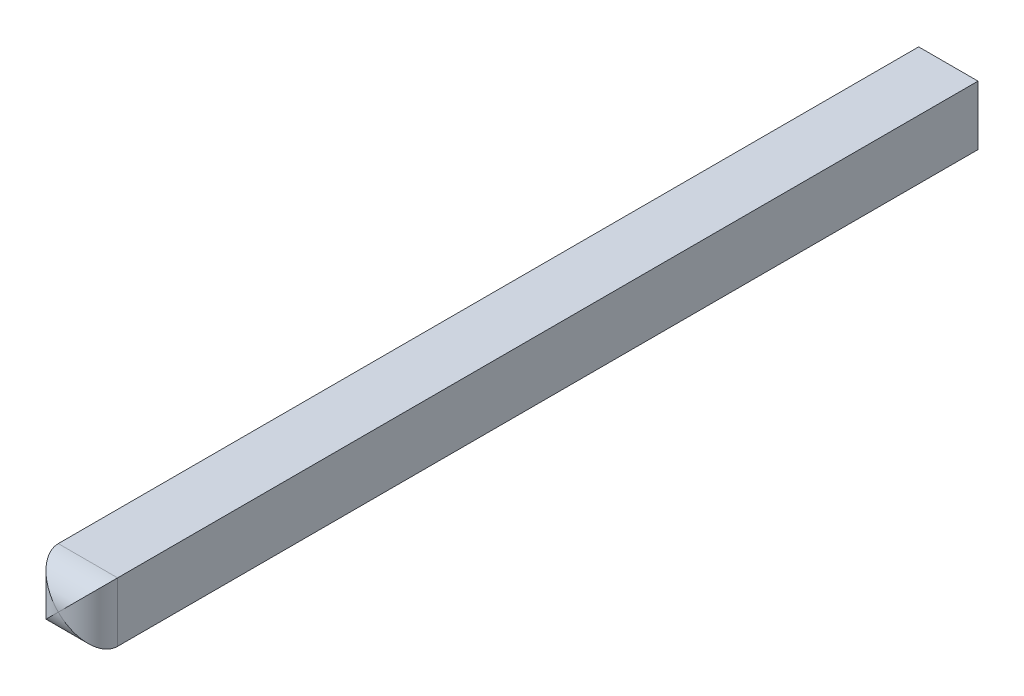
SolidWorks part; units mm, degrees
ref_plane "Front Plane" through (0, 0, 0) normal (0, 0, 1) x (1, 0, 0)
ref_plane "Top Plane" through (0, 0, 0) normal (0, 1, 0) x (1, 0, 0)
ref_plane "Right Plane" through (0, 0, 0) normal (1, 0, 0) x (0, 0, -1)
sketch "Sketch1" plane through (0, 0, 0) normal (0, 0, 1) x (1, 0, 0)
  line L0 (-11.7143, 10.1429) -> (-11.7143, -9.8571)
  line L1 (-11.7143, -9.8571) -> (8.2857, -9.8571)
  line L2 (8.2857, -9.8571) -> (8.2857, 10.1429)
  line L3 (8.2857, 10.1429) -> (-11.7143, 10.1429)
  dimension "D1" = 20
  dimension "D2" = 20
extrude "Boss-Extrude1" add sketch "Sketch1" along normal blind 300
fillet "Fillet2" radius 10 4 edges at (-11.7143, 0.1429, 300) (-1.7143, -9.8571, 300) (8.2857, 0.1429, 300) (-1.7143, 10.1429, 300)
